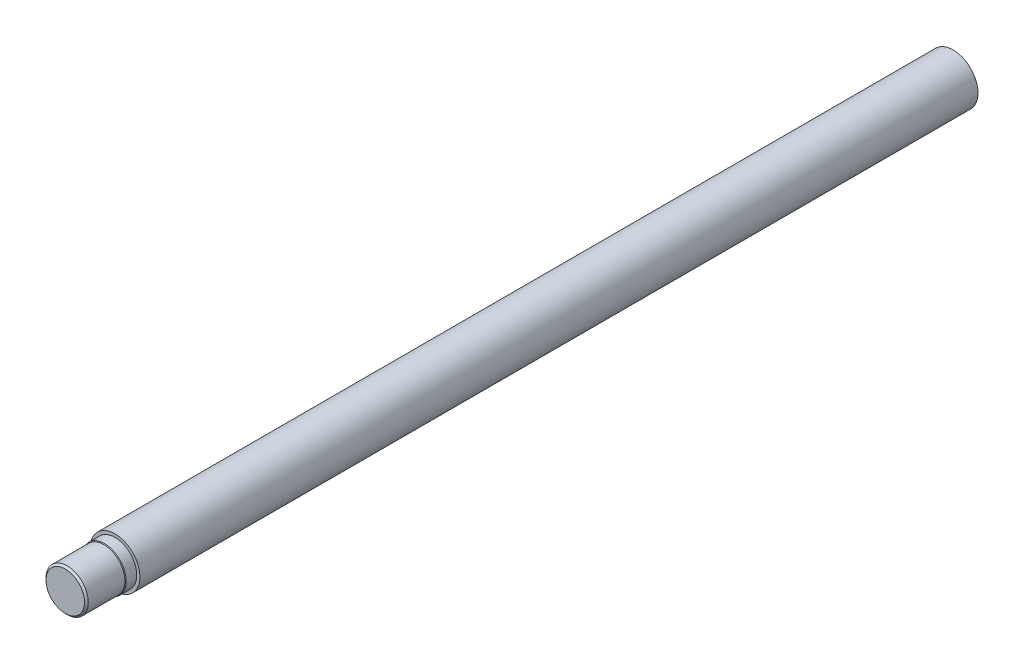
SolidWorks part; units mm, degrees
ref_plane "Front Plane" through (0, 0, 0) normal (0, 0, 1) x (1, 0, 0)
ref_plane "Top Plane" through (0, 0, 0) normal (0, 1, 0) x (1, 0, 0)
ref_plane "Right Plane" through (0, 0, 0) normal (1, 0, 0) x (0, 0, -1)
sketch "Sketch1" plane through (0, 0, 0) normal (0, 0, 1) x (1, 0, 0)
  circle A0 centre (0, 0) radius 40
  dimension "D1" = 80
extrude "Boss-Extrude1" add sketch "Sketch1" along normal mid plane 1428
cosmetic thread "Cosmetic Thread2" parameters "D1"=5, "D2"=78.5
sketch "Sketch2" plane through (0, 0, 0) normal (1, 0, 0) x (0, 0, -1)
  line L0 (0, 0) -> (-271.6663, 0) construction
  line L1 (-714, 34) -> (-654, 34)
  line L2 (-654, 34) -> (-654, 35)
  line L3 (-654, 35) -> (-634, 35)
  line L4 (-634, 35) -> (-634, 52.8523)
  line L5 (-634, 52.8523) -> (-714, 52.8523)
  line L6 (-714, 52.8523) -> (-714, 34)
  line L7 (-714, 40) -> (-714, -40) construction
  point P7 (-654, 34.5)
  dimension "D1" = 68
  dimension "D2" = 70
  dimension "D3" = 60
  dimension "D4" = 80
revolve "Cut-Revolve1" cut sketch "Sketch2" angle 360 about L0
cosmetic thread "Cosmetic Thread1" parameters "D1"=50, "D2"=66
chamfer "Chamfer1" distance 3 angle 45 2 edges at (-35, 0, 654) (-34, 0, 714)
sketch "Sketch3" plane through (0, 0, 0) normal (0, 1, 0) x (1, 0, 0)
  line L0 (0, 0) -> (0, -643.2475) construction
  line L1 (-35, -634) -> (35, -634) construction
  line L2 (93.9142, -184) -> (37.5, -184)
  line L3 (93.9142, -184) -> (93.9142, -634)
  line L4 (93.9142, -634) -> (37.5, -634)
  line L5 (37.5, -184) -> (37.5, -634)
  dimension "D1" = 75
  dimension "D2" = 450
revolve "Cut-Revolve2" [suppressed] cut sketch "Sketch3" angle 360 about L0
